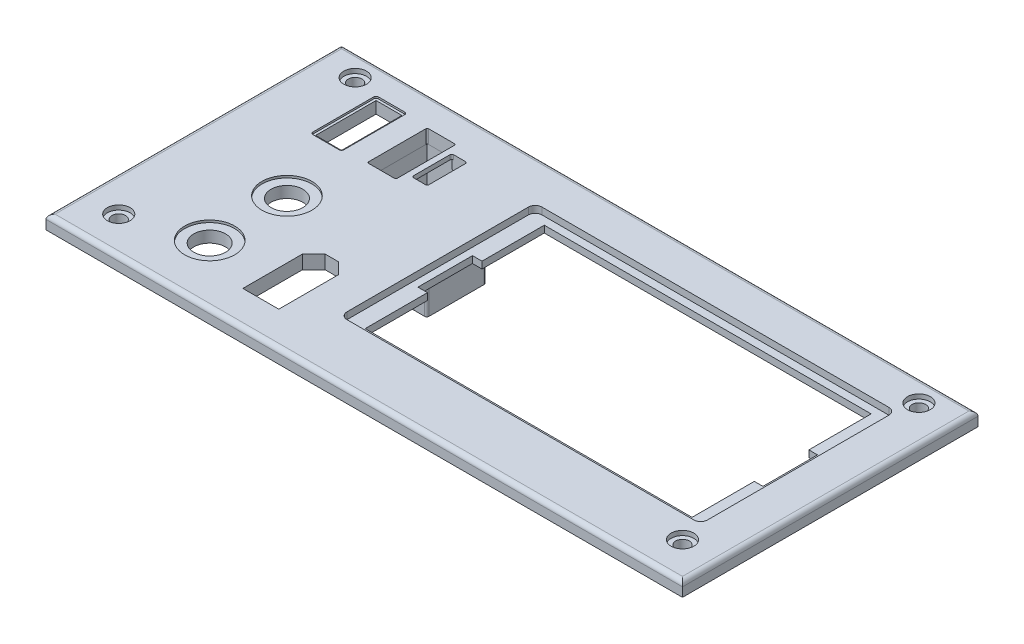
SolidWorks part; units mm, degrees
ref_plane "Спереди" through (0, 0, 0) normal (0, 0, 1) x (1, 0, 0)
ref_plane "Сверху" through (0, 0, 0) normal (0, 1, 0) x (1, 0, 0)
ref_plane "Справа" through (0, 0, 0) normal (1, 0, 0) x (0, 0, -1)
sketch "Эскиз1" plane through (0, 0, 0) normal (0, 1, 0) x (1, 0, 0)
  line L1 (-60, 30) -> (80, 30)
  line L2 (-60, 30) -> (-60, -35)
  line L3 (-60, -35) -> (80, -35)
  line L4 (80, 30) -> (80, -35)
  line L5 (-60, 30) -> (80, -35) construction
  line L6 (-60, -35) -> (80, 30) construction
  point P0 (0, 0)
  dimension "D1" = 65
  dimension "D2" = 140
extrude "Передняя панель основа" add sketch "Эскиз1" along normal blind 3
sketch "Эскиз2" plane through (0, 3, 0) normal (0, 1, 0) x (1, 0, 0)
  line L1 (71, 20.9) -> (-8.3, 20.9)
  line L2 (71, 20.9) -> (71, -22)
  line L3 (71, -22) -> (-8.3, -22)
  line L4 (-8.3, 20.9) -> (-8.3, -22)
  line L5 (71, 20.9) -> (-8.3, -22) construction
  line L6 (71, -22) -> (-8.3, 20.9) construction
  point P0 (31.35, -0.55)
  dimension "D1" = 42.9
  dimension "D2" = 79.3
  dimension "D3" = 13
  dimension "D4" = 9
extrude "Внешняя рамка модуля" cut sketch "Эскиз2" against normal blind 1.5
fillet "Уголки скругления рамки выреза модуля" radius 1.5 4 edges at (71, 2.25, 22) (-8.3, 2.25, 22) (71, 2.25, -20.9) (-8.3, 2.25, -20.9)
sketch "Эскиз3" plane through (0, 1.5, 0) normal (0, 1, 0) x (1, 0, 0)
  line L0 (-60, -35) -> (80, -35) construction
  line L1 (-4.6, 19.2) -> (67.3, 19.2)
  line L2 (-4.6, 19.2) -> (-4.6, -20.2)
  line L3 (-4.6, -20.2) -> (67.3, -20.2)
  line L4 (67.3, 19.2) -> (67.3, -20.2)
  line L5 (-4.6, 19.2) -> (67.3, -20.2) construction
  line L6 (-4.6, -20.2) -> (67.3, 19.2) construction
  line L7 (69.5, 20.9) -> (-6.8, 20.9) construction
  line L8 (-6.8, -22) -> (69.5, -22) construction
  line L9 (71, -20.5) -> (71, 19.4) construction
  line L10 (-8.3, 19.4) -> (-8.3, -20.5) construction
  point P0 (31.35, -0.5)
  dimension "D1" = 39.4
  dimension "D2" = 71.9
  dimension "D3" = 14.8
  dimension "D4" = 12.7
  dimension "D5" = 1.7
  dimension "D6" = 1.8
  dimension "D7" = 3.7
  dimension "D8" = 3.7
extrude "Вырез тела модуля" cut sketch "Эскиз3" against normal blind 3
sketch "Эскиз4" plane through (0, 1.5, 0) normal (0, 1, 0) x (1, 0, 0)
  line L0 (-4.6, 19.2) -> (-4.6, -20.2) construction
  line L1 (-2.5, -6.5) -> (-6.7, -6.5)
  line L2 (-2.5, -6.5) -> (-2.5, 5.5)
  line L3 (-2.5, 5.5) -> (-6.7, 5.5)
  line L4 (-6.7, -6.5) -> (-6.7, 5.5)
  line L5 (-2.5, -6.5) -> (-6.7, 5.5) construction
  line L6 (-2.5, 5.5) -> (-6.7, -6.5) construction
  line L7 (69.2, -6.5) -> (69.2, 5.5)
  line L8 (69.2, -6.5) -> (65, -6.5)
  line L9 (65, -6.5) -> (65, 5.5)
  line L10 (69.2, 5.5) -> (65, 5.5)
  point P0 (-4.6, -0.5)
  dimension "D1" = 12
  dimension "D2" = 4.2
  dimension "D3" = 2
extrude "Ушки модуля" cut sketch "Эскиз4" against normal blind 3
sketch "Эскиз5" plane through (0, 3, 0) normal (0, 1, 0) x (1, 0, 0)
  line L1 (-60, -35) -> (80, -35) construction
  line L2 (-60, 30) -> (-60, -35) construction
  circle A0 centre (-37, -5) radius 5.5
  circle A1 centre (-37, -22) radius 5.5
  dimension "D1" = 11
  dimension "D2" = 11
  dimension "D3" = 13
  dimension "D4" = 23
  dimension "D5" = 17
extrude "Внешние кольца под бананы" cut sketch "Эскиз5" against normal blind 0.5
sketch "Эскиз6" plane through (0, 2.5, 0) normal (0, 1, 0) x (1, 0, 0)
  circle A0 centre (-37, -5) radius 3.5
  circle A1 centre (-37, -22) radius 3.5
  dimension "D1" = 7
  dimension "D2" = 7
extrude "Вырез под бананы" cut sketch "Эскиз6" against normal blind 3
sketch "Эскиз7" plane through (0, 3, 0) normal (0, 1, 0) x (1, 0, 0)
  line L1 (-46.3, 23.9) -> (-39.5, 23.9)
  line L2 (-46.3, 23.9) -> (-46.3, 9.5)
  line L3 (-46.3, 9.5) -> (-39.5, 9.5)
  line L4 (-39.5, 23.9) -> (-39.5, 9.5)
  line L5 (-46.3, 23.9) -> (-39.5, 9.5) construction
  line L6 (-46.3, 9.5) -> (-39.5, 23.9) construction
  line L10 (-8.3, 19.4) -> (-8.3, -20.5) construction
  line L11 (69.5, 20.9) -> (-6.8, 20.9) construction
  circle A0 centre (-37, -5) radius 5.5 construction
  point P0 (-42.9, 16.7)
  dimension "D1" = 14.4
  dimension "D2" = 6.8
  dimension "D4" = 2.5
extrude "Внешняя рамка USB" cut sketch "Эскиз7" against normal blind 0.4
sketch "Эскиз8" plane through (0, 2.6, 0) normal (0, 1, 0) x (1, 0, 0)
  line L0 (-39.5, 23.9) -> (-46.3, 23.9) construction
  line L1 (-45.75, 23.35) -> (-40.05, 23.35)
  line L2 (-45.75, 23.35) -> (-45.75, 10.05)
  line L3 (-45.75, 10.05) -> (-40.05, 10.05)
  line L4 (-40.05, 23.35) -> (-40.05, 10.05)
  line L5 (-45.75, 23.35) -> (-40.05, 10.05) construction
  line L6 (-45.75, 10.05) -> (-40.05, 23.35) construction
  line L7 (-46.3, 9.5) -> (-39.5, 9.5) construction
  line L8 (-46.3, 23.9) -> (-46.3, 9.5) construction
  line L9 (-39.5, 9.5) -> (-39.5, 23.9) construction
  point P0 (-42.9, 16.7)
  dimension "D1" = 13.3
  dimension "D2" = 5.7
  dimension "D3" = 0.55
  dimension "D4" = 0.55
  dimension "D5" = 0.55
  dimension "D6" = 0.55
extrude "USB" cut sketch "Эскиз8" against normal blind 3
fillet "Скругление уголков 1 USB" radius 0.5 4 edges at (-46.3, 2.8, -9.5) (-39.5, 2.8, -9.5) (-39.5, 2.8, -23.9) (-46.3, 2.8, -23.9)
sketch "Эскиз9" plane through (0, 3, 0) normal (0, 1, 0) x (1, 0, 0)
  line L0 (-24.2, -27.5) -> (-16.3, -27.5)
  line L1 (-16.3, -27.5) -> (-16.3, -14.4)
  line L2 (-16.3, -14.4) -> (-18.8, -11.9)
  line L3 (-18.8, -11.9) -> (-21.7, -11.9)
  line L4 (-21.7, -11.9) -> (-24.2, -14.4)
  line L5 (-24.2, -14.4) -> (-24.2, -27.5)
  line L6 (-46.3, 23.4) -> (-46.3, 10) construction
  line L7 (-60, -35) -> (80, -35) construction
  line L8 (-8.3, 19.4) -> (-8.3, -20.5) construction
  line L9 (-60, 30) -> (-60, -35) construction
  circle A3 centre (-37, -22) radius 5.5 construction
  point P8 (-20.25, -27.5)
  point P9 (-20.25, -11.9)
  dimension "D4" = 7.5
  dimension "D1" = 7.9
  dimension "D2" = 15.6
  dimension "D3" = 2.5
  dimension "D5" = 8
  dimension "D6" = 12.8
  dimension "D7" = 35.8
extrude "XT60 на передней панели" cut sketch "Эскиз9" against normal through all
sketch "Эскиз10" plane through (0, 3, 0) normal (0, 1, 0) x (1, 0, 0)
  line L0 (80, 30) -> (-60, 30) construction
  line L1 (-60, 30) -> (-60, -35) construction
  line L2 (80, -35) -> (80, 30) construction
  line L3 (-60, -35) -> (80, -35) construction
  circle A0 centre (-52, 25) radius 1.5
  circle A1 centre (72, 25) radius 1.5
  circle A2 centre (72, -27) radius 1.5
  circle A3 centre (-52, -27) radius 1.5
  dimension "D1" = 3
  dimension "D2" = 5
  dimension "D3" = 8
  dimension "D5" = 8
  dimension "D6" = 5
  dimension "D7" = 8
  dimension "D8" = 8
  dimension "D9" = 8
  dimension "D10" = 8
  dimension "D4" = 2
extrude "Отверстия крепления передней панели к корпусу" cut sketch "Эскиз10" against normal through all
sketch "Эскиз13" plane through (0, 3, 0) normal (0, 1, 0) x (1, 0, 0)
  circle A0 centre (-52, 25) radius 2.5
  circle A1 centre (72, 25) radius 2.5
  circle A2 centre (72, -27) radius 2.5
  circle A3 centre (-52, -27) radius 2.5
  dimension "D1" = 5
  dimension "D2" = 2
extrude "Фаска под головку болта передней панели" cut sketch "Эскиз13" against normal blind 1
fillet "Скругление1" radius 1 4 edges at (10, 3, 35) (80, 3, 2.5) (-60, 3, 2.5) (10, 3, -30)
sketch "Эскиз14" plane through (0, 3, 0) normal (0, 1, 0) x (1, 0, 0)
  line L0 (-28.2, 10.15) -> (-34.5, 10.15)
  line L1 (-34.5, 10.15) -> (-34.5, 23.35)
  line L2 (-34.5, 23.35) -> (-28.2, 23.35)
  line L3 (-28.2, 23.35) -> (-28.2, 25.9)
  line L4 (-28.2, 25.9) -> (-26.9, 25.9)
  line L5 (-26.9, 25.9) -> (-26.9, 21.15)
  line L6 (-26.9, 21.15) -> (-23.5, 21.15)
  line L7 (-23.5, 21.15) -> (-23.5, 12.35)
  line L8 (-23.5, 12.35) -> (-26.9, 12.35)
  line L9 (-26.9, 12.35) -> (-26.9, 7.6)
  line L10 (-26.9, 7.6) -> (-28.2, 7.6)
  line L11 (-28.2, 7.6) -> (-28.2, 10.15)
  line L12 (-40.05, 23.35) -> (-45.75, 23.35) construction
  circle A0 centre (-37, -5) radius 3.5 construction
  dimension "D1" = 13.2
  dimension "D2" = 11
  dimension "D3" = 6.3
  dimension "D4" = 1.3
  dimension "D5" = 3.4
  dimension "D6" = 8.8
  dimension "D7" = 18.3
  dimension "D8" = 2.5
extrude "Вырез-Вытянуть1" cut sketch "Эскиз14" against normal blind 3
fillet "Скругление2" radius 0.4 2 edges at (-23.5, 1.5, -12.35) (-23.5, 1.5, -21.15)
fillet "Скругление3" radius 0.3 2 edges at (-34.5, 1.5, -10.15) (-34.5, 1.5, -23.35)
sketch "Эскиз15" plane through (0, 3, 0) normal (0, 1, 0) x (1, 0, 0)
  line L1 (-28.2, 26) -> (-26.9, 26)
  line L2 (-28.2, 26) -> (-28.2, 7.6)
  line L3 (-28.2, 7.6) -> (-26.9, 7.6)
  line L4 (-26.9, 26) -> (-26.9, 7.6)
  line L5 (-28.2, 26) -> (-26.9, 7.6) construction
  line L6 (-28.2, 7.6) -> (-26.9, 26) construction
  line L11 (-26.9, 25.9) -> (-28.2, 25.9) construction
  line L12 (-28.2, 7.6) -> (-26.9, 7.6) construction
  line L15 (-28.2, 25.9) -> (-28.2, 23.35) construction
  point P0 (-27.55, 16.8)
  point P10 (-27.55, 7.6)
  dimension "D1" = 18.4
extrude "Бобышка-Вытянуть1" add sketch "Эскиз15" against normal blind 1
fillet "Скругление4" radius 0.3 2 edges at (-28.2, 2.5, -10.15) (-28.2, 2.5, -23.35)
fillet "Скругление5" radius 0.4 2 edges at (-26.9, 2.5, -12.35) (-26.9, 2.5, -21.15)
sketch "Эскиз17" plane through (0, 0, 0) normal (0, -1, 0) x (1, 0, 0)
  line L0 (-34.6184, -9.9961) -> (-28.3093, -9.9961)
  line L1 (-28.3093, -9.9961) -> (-28.3093, -7.5533)
  line L2 (-28.3093, -7.5533) -> (-26.7705, -7.5533)
  line L3 (-26.7705, -7.5533) -> (-26.7705, -12.1697)
  line L4 (-26.7705, -12.1697) -> (-23.4044, -12.1697)
  line L5 (-23.4044, -12.1697) -> (-23.4044, -21.2455)
  line L6 (-23.4044, -21.2455) -> (-26.7705, -21.2455)
  line L7 (-26.7705, -21.2455) -> (-26.7705, -25.9546)
  line L8 (-26.7705, -25.9546) -> (-28.3093, -25.9546)
  line L9 (-28.3093, -25.9546) -> (-28.3093, -23.4086)
  line L10 (-28.3093, -23.4086) -> (-34.6184, -23.4086)
  line L11 (-34.6184, -23.4086) -> (-34.6184, -9.9961)
extrude "Вытянуть-Тонкостенный1" add sketch "Эскиз17" along normal blind 20 thin thin type one direction wall 2
fillet "Скругление6" radius 0.5 12 edges at (-24.7705, -10, -23.2455) (-24.7705, -10, -27.9546) (-30.3093, -10, -27.9546) (-30.3093, -10, -25.4086) (-36.6184, -10, -25.4086) (-36.6184, -10, -7.9961) (-30.3093, -10, -7.9961) (-30.3093, -10, -5.5533) (-21.4044, -10, -23.2455) (-24.7705, -10, -10.1697) (-21.4044, -10, -10.1697) (-24.7705, -10, -5.5533)
